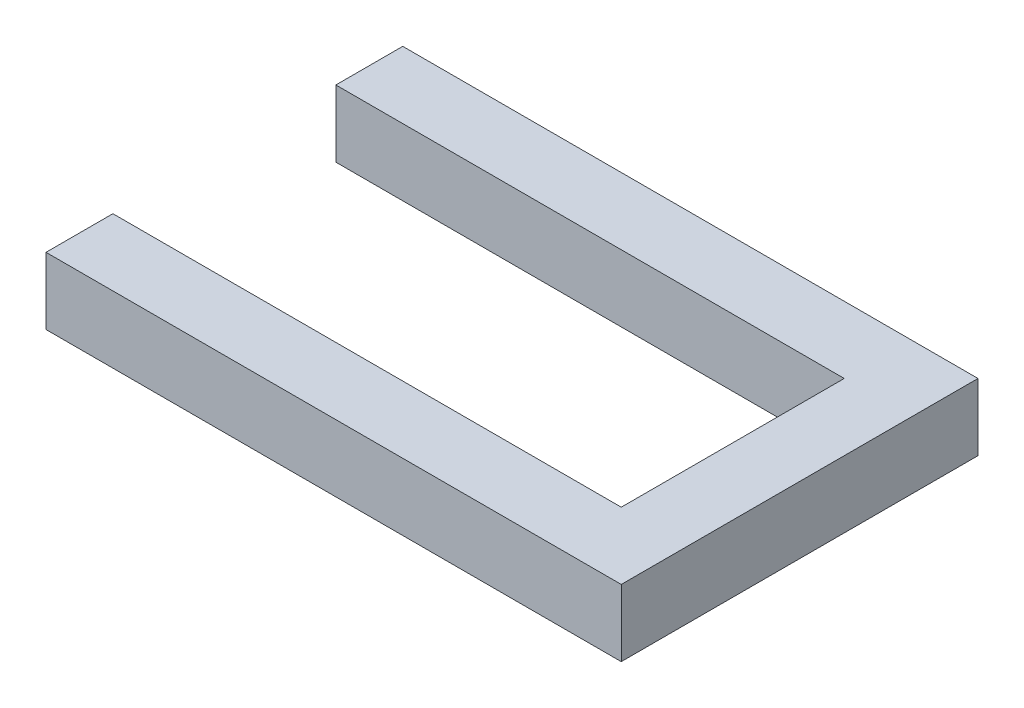
SolidWorks part; units mm, degrees
ref_plane "Front Plane" through (0, 0, 0) normal (0, 0, 1) x (1, 0, 0)
ref_plane "Top Plane" through (0, 0, 0) normal (0, 1, 0) x (1, 0, 0)
ref_plane "Right Plane" through (0, 0, 0) normal (1, 0, 0) x (0, 0, -1)
sketch "Sketch1" plane through (0, 0, 0) normal (0, 0, 1) x (1, 0, 0)
  line L1 (-88.9, 6.35) -> (-127, 6.35)
  line L2 (-88.9, 6.35) -> (-88.9, -31.75)
  line L3 (-88.9, -31.75) -> (-127, -31.75)
  line L4 (-127, 6.35) -> (-127, -31.75)
  line L5 (-88.9, 6.35) -> (-88.9, 0) construction
  line L6 (-26.4, 6.35) -> (-87.9, 6.35) construction
  dimension "D1" = 38.1
  dimension "D2" = 38.1
extrude "Boss-Extrude1" add sketch "Sketch1" along normal blind 101.6 and the other way blind 101.6
sketch "Sketch2" plane through (-127, 0, 0) normal (-1, 0, 0) x (0, 0, 1)
  line L0 (-101.6, -31.75) -> (101.6, -31.75) construction
  line L1 (101.6, 6.35) -> (63.5, 6.35)
  line L2 (101.6, 6.35) -> (101.6, -31.75)
  line L3 (101.6, -31.75) -> (63.5, -31.75)
  line L4 (63.5, 6.35) -> (63.5, -31.75)
  line L6 (-101.6, 6.35) -> (-63.5, 6.35)
  line L7 (-101.6, 6.35) -> (-101.6, -31.75)
  line L8 (-101.6, -31.75) -> (-63.5, -31.75)
  line L9 (-63.5, 6.35) -> (-63.5, -31.75)
  dimension "D1" = 38.1
  dimension "D2" = 38.1
extrude "Boss-Extrude2" add sketch "Sketch2" along normal up to surface (289.56 mm away)
